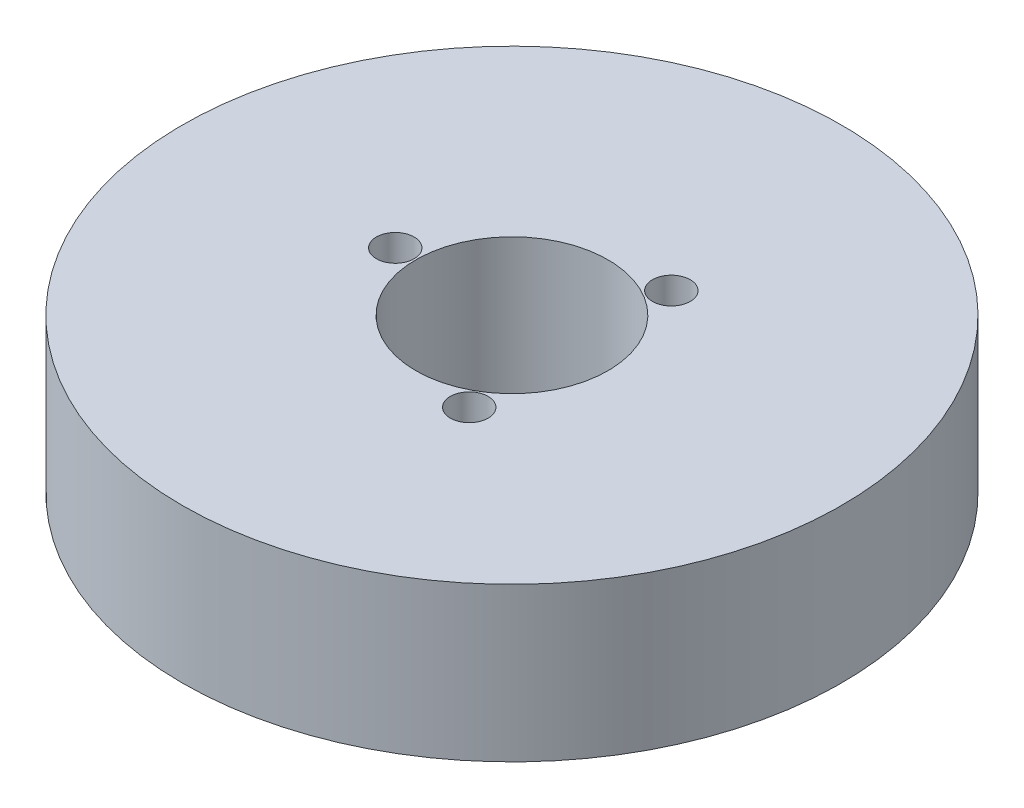
SolidWorks part; units mm, degrees
ref_plane "Front Plane" through (0, 0, 0) normal (0, 0, 1) x (1, 0, 0)
ref_plane "Top Plane" through (0, 0, 0) normal (0, 1, 0) x (1, 0, 0)
ref_plane "Right Plane" through (0, 0, 0) normal (1, 0, 0) x (0, 0, -1)
sketch "Sketch1" plane through (0, 0, 0) normal (0, 1, 0) x (1, 0, 0)
  circle A0 centre (0, 0) radius 60
  dimension "FLANGE_OD" = 120
extrude "Boss-Extrude1" add sketch "Sketch1" along normal blind 28
sketch "Sketch2" plane through (0, 0, 0) normal (0, 1, 0) x (1, 0, 0)
  circle A0 centre (0, 0) radius 17.5
  dimension "BORE_D" = 35
extrude "Cut-Extrude1" cut sketch "Sketch2" along normal through all
sketch "Sketch3" plane through (0, 28, 0) normal (0, 1, 0) x (1, 0, 0)
  circle A0 centre (0, 0) radius 21.2444 construction
  circle A1 centre (-21.2444, 0) radius 3.4407
  dimension "BOLT_D" = 6.8813
  dimension "BOLT_PCD" = 42.4889
extrude "Cut-Extrude2" cut sketch "Sketch3" against normal blind 20.4305
pattern_circular "CirPattern1" count 3 over 360 about axis through (0, 0, 0) along (0, 1, 0) of "Cut-Extrude2"
